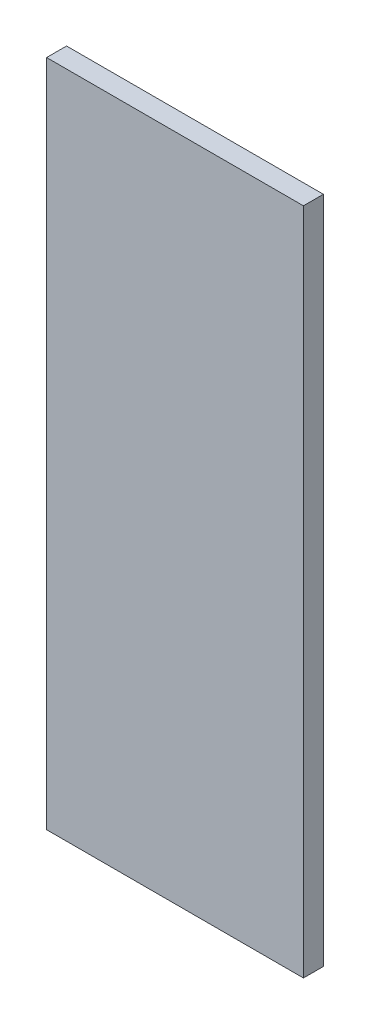
SolidWorks part; units mm, degrees
ref_plane "Front Plane" through (0, 0, 0) normal (0, 0, 1) x (1, 0, 0)
ref_plane "Top Plane" through (0, 0, 0) normal (0, 1, 0) x (1, 0, 0)
ref_plane "Right Plane" through (0, 0, 0) normal (1, 0, 0) x (0, 0, -1)
sketch "Sketch1" plane through (0, 0, 0) normal (0, 0, 1) x (1, 0, 0)
  line L1 (-245.05, 0) -> (0, 0)
  line L2 (-245.05, 0) -> (-245.05, -638.1)
  line L3 (-245.05, -638.1) -> (0, -638.1)
  line L4 (0, 0) -> (0, -638.1)
  dimension "D1" = 638.1
  dimension "D2" = 245.05
extrude "Boss-Extrude1" add sketch "Sketch1" along normal blind 19.05
